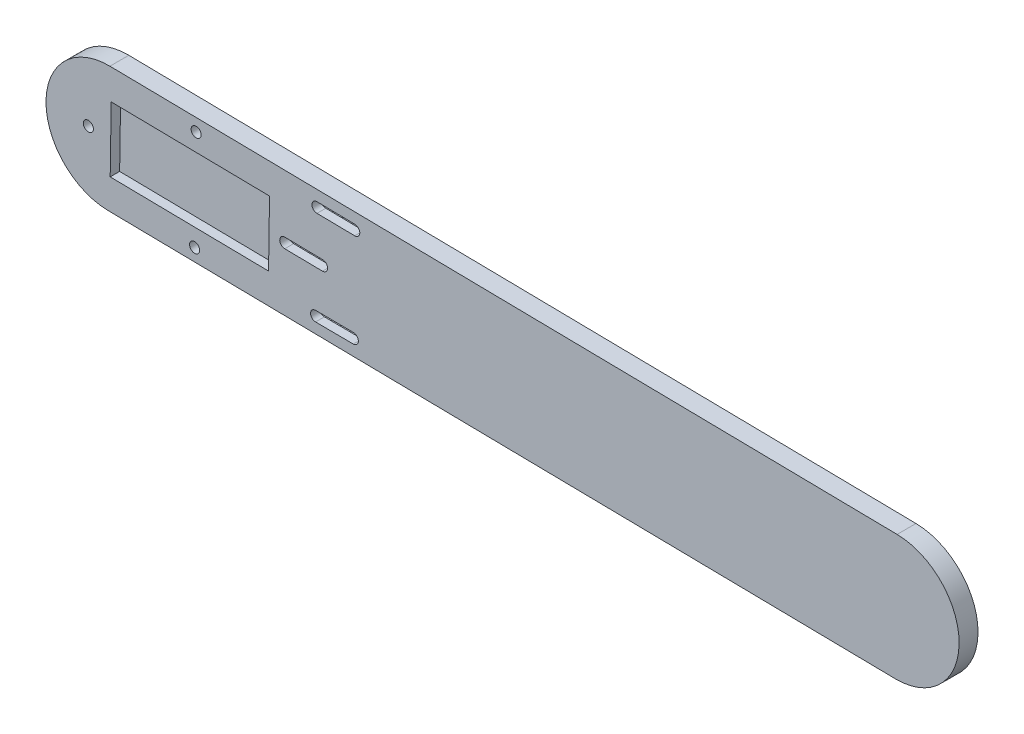
SolidWorks part; units mm, degrees
ref_plane "Front Plane" through (0, 0, 0) normal (0, 0, 1) x (1, 0, 0)
ref_plane "Top Plane" through (0, 0, 0) normal (0, 1, 0) x (1, 0, 0)
ref_plane "Right Plane" through (0, 0, 0) normal (1, 0, 0) x (0, 0, -1)
sketch "Sketch1" plane through (0, 0, 0) normal (0, 0, 1) x (1, 0, 0)
  line L0 (53.4525, 19.6302) -> (303.4239, 15.8492)
  line L1 (302.8189, -24.1462) -> (52.8475, -20.3652)
  arc A0 (303.4239, 15.8492) -> (302.8189, -24.1462) centre (303.1214, -4.1485) cw
  arc A1 (52.8475, -20.3652) -> (53.4525, 19.6302) centre (53.15, -0.3675) cw
extrude "Boss-Extrude1" add sketch "Sketch1" along normal blind 6
sketch "Sketch2" plane through (0, 0, 0) normal (0, 0, -1) x (-1, 0, 0)
  circle A0 centre (-53.15, -0.3675) radius 12.2
  dimension "D1" = 24.4
extrude "Boss-Extrude2" add sketch "Sketch2" along normal offset from surface (5.25 mm away) 0.25 offset beyond the face yes
sketch "Sketch4" plane through (0, 0, 6) normal (0, 0, 1) x (1, 0, 0)
  line L0 (104.1372, 9.2577) -> (53.8524, 10.0183)
  line L1 (53.8524, 10.0183) -> (53.538, -10.7698)
  line L2 (53.538, -10.7698) -> (103.8228, -11.5304)
  line L3 (103.8228, -11.5304) -> (104.1372, 9.2577)
  line L4 (94.1294, 8.8184) -> (93.8328, -10.7886) construction
  line L5 (54.4354, 9.5095) -> (94.0402, 8.9104) construction
  line L6 (93.7409, -10.8779) -> (54.1361, -10.2788) construction
  line L7 (54.0469, -10.1868) -> (54.3434, 9.4202) construction
  dimension "D1" = 10
  dimension "D2" = 0.5
  dimension "D3" = 0.5
  dimension "D4" = 0.5
extrude "Cut-Extrude1" cut sketch "Sketch4" against normal blind 3
sketch "Sketch5" plane through (0, 0, 6) normal (0, 0, 1) x (1, 0, 0)
  circle A0 centre (80.8294, 15.2156) radius 1.6
  circle A1 centre (46.6019, -0.2685) radius 1.6
  circle A2 centre (80.3455, -16.7764) radius 1.6
extrude "Cut-Extrude2" cut sketch "Sketch5" against normal up to next
sketch "Sketch6" plane through (0, 0, 0) normal (0, 0, -1) x (-1, 0, 0)
  circle A0 centre (-80.3455, -16.7764) radius 2.75
  circle A1 centre (-80.8294, 15.2156) radius 2.75
  dimension "D1" = 5.5
extrude "Cut-Extrude3" cut sketch "Sketch6" against normal blind 3.2
sketch "Sketch7" plane through (0, 0, -5.25) normal (0, 0, -1) x (-1, 0, 0)
  circle A0 centre (-46.6019, -0.2685) radius 2.75
  dimension "D1" = 5.5
extrude "Cut-Extrude4" cut sketch "Sketch7" against normal blind 3.2
sketch "Sketch8" plane through (0, 0, 0) normal (0, 0, -1) x (-1, 0, 0)
  line L0 (-119.2051, 13.6351) -> (-118.7514, -16.3615) construction
  line L1 (-118.9783, -1.3632) -> (-108.9783, -1.212) construction
  line L2 (-108.9783, 0.3879) -> (-121.0025, 0.206)
  line L3 (-303.4239, 15.8492) -> (-53.4525, 19.6302) construction
  line L4 (-108.9783, -2.8121) -> (-120.9541, -2.9933)
  line L5 (-118.7514, -16.3615) -> (-130.7514, -16.543) construction
  line L6 (-52.8475, -20.3652) -> (-302.8189, -24.1462) construction
  line L7 (-130.7401, -18.1428) -> (-118.7514, -18.0578)
  line L8 (-118.7742, -14.8578) -> (-130.7628, -14.9432)
  line L9 (-119.2051, 13.6351) -> (-131.2051, 13.4536) construction
  line L10 (-119.2051, 12.0351) -> (-131.1809, 11.8537)
  line L11 (-131.2293, 15.0534) -> (-119.2293, 15.2349)
  arc A0 (-119.2051, 12.0351) -> (-119.2293, 15.2349) centre (-119.2051, 13.6351) ccw
  arc A4 (-121.0025, 0.206) -> (-120.9541, -2.9933) centre (-120.9783, -1.3936) ccw
  arc A5 (-108.9783, -2.8121) -> (-108.9783, 0.3879) centre (-108.9783, -1.2121) ccw
  arc A6 (-130.7628, -14.9432) -> (-130.7401, -18.1428) centre (-130.7514, -16.543) ccw
  arc A7 (-118.7514, -18.0578) -> (-118.7742, -14.8578) centre (-118.7628, -16.4578) ccw
  arc A8 (-131.1809, 11.8537) -> (-131.2293, 15.0534) centre (-131.2051, 13.4536) cw
  dimension "D1" = 3.2
  dimension "D4" = 1.6
  dimension "D6" = 1.6
  dimension "D2" = 12
  dimension "D3" = 10
  dimension "D5" = 12
  dimension "D7" = 12
extrude "Cut-Extrude5" cut sketch "Sketch8" against normal up to next
sketch "Sketch9" plane through (0, 0, 0) normal (0, 0, -1) x (-1, 0, 0)
  arc A0 (-120.2172, -18.6289) -> (-120.2852, -14.1395) centre (-118.7514, -16.3615) ccw
  arc A1 (-120.671, 11.3676) -> (-120.7389, 15.8571) centre (-119.2051, 13.6351) ccw
  arc A2 (-120.2852, -14.1395) -> (-123.2849, -14.1849) centre (-121.7511, -16.4069) ccw
  arc A3 (-120.7389, 15.8571) -> (-123.7386, 15.8117) centre (-122.2048, 13.5897) ccw
  arc A4 (-123.2849, -14.1849) -> (-126.2845, -14.2303) centre (-124.7507, -16.4523) ccw
  arc A5 (-123.7386, 15.8117) -> (-126.7383, 15.7663) centre (-125.2044, 13.5442) ccw
  arc A6 (-126.2845, -14.2303) -> (-129.2842, -14.2757) centre (-127.7504, -16.4978) ccw
  arc A7 (-126.7383, 15.7663) -> (-129.7379, 15.7208) centre (-128.2041, 13.4988) ccw
  arc A8 (-129.2842, -14.2757) -> (-129.2162, -18.7652) centre (-130.75, -16.5432) ccw
  arc A9 (-129.7379, 15.7208) -> (-129.6699, 11.2314) centre (-131.2038, 13.4534) ccw
  arc A14 (-110.4441, -3.4796) -> (-110.5121, 1.0099) centre (-108.9783, -1.2121) ccw
  arc A15 (-110.5121, 1.0099) -> (-113.5117, 0.9645) centre (-111.9779, -1.2576) ccw
  arc A16 (-113.5117, 0.9645) -> (-116.5114, 0.9191) centre (-114.9776, -1.303) ccw
  arc A17 (-116.5114, 0.9191) -> (-119.5111, 0.8736) centre (-117.9772, -1.3484) ccw
  arc A18 (-119.5111, 0.8736) -> (-119.4431, -3.6158) centre (-120.9769, -1.3938) ccw
  arc A19 (-113.4438, -3.525) -> (-110.4441, -3.4796) centre (-111.9779, -1.2576) ccw
  arc A20 (-116.4434, -3.5704) -> (-113.4438, -3.525) centre (-114.9776, -1.303) ccw
  arc A21 (-119.4431, -3.6158) -> (-116.4434, -3.5704) centre (-117.9772, -1.3484) ccw
  arc A22 (-123.2169, -18.6744) -> (-120.2172, -18.6289) centre (-121.7511, -16.4069) ccw
  arc A23 (-126.2166, -18.7198) -> (-123.2169, -18.6744) centre (-124.7507, -16.4523) ccw
  arc A24 (-129.2162, -18.7652) -> (-126.2166, -18.7198) centre (-127.7504, -16.4978) ccw
  arc A25 (-123.6706, 11.3222) -> (-120.671, 11.3676) centre (-122.2048, 13.5897) ccw
  arc A26 (-126.6703, 11.2768) -> (-123.6706, 11.3222) centre (-125.2044, 13.5442) ccw
  arc A27 (-129.6699, 11.2314) -> (-126.6703, 11.2768) centre (-128.2041, 13.4988) ccw
  dimension "D1" = 5.4
  dimension "D2" = 5
extrude "Cut-Extrude6" cut sketch "Sketch9" against normal blind 3.2
